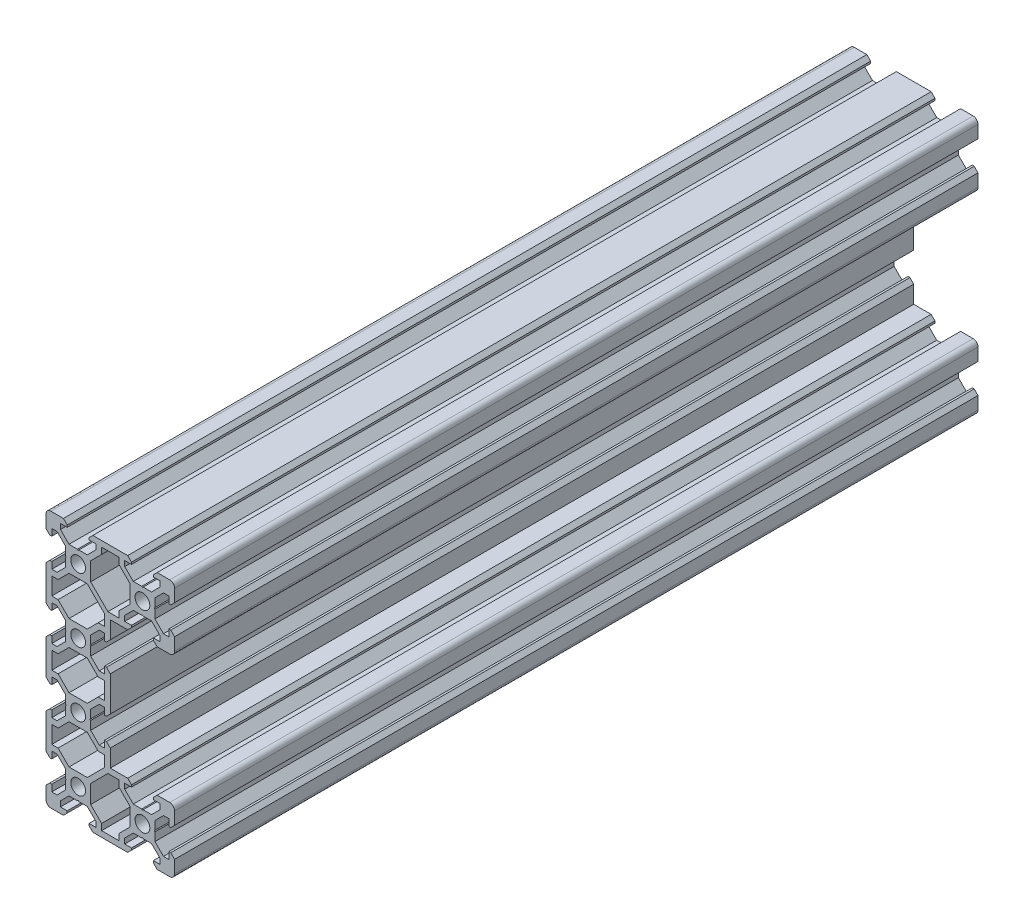
SolidWorks part; units mm, degrees
material "6061-T6 (SS)"
ref_plane "Front Plane" through (0, 0, 0) normal (0, 0, 1) x (1, 0, 0)
ref_plane "Top Plane" through (0, 0, 0) normal (0, 1, 0) x (1, 0, 0)
ref_plane "Right Plane" through (0, 0, 0) normal (1, 0, 0) x (0, 0, -1)
sketch "Sketch1" plane through (0, 0, 0) normal (0, 0, 1) x (1, 0, 0)
  line L0 (-20, -38.5) -> (-20, 38.5)
  line L1 (-18.5, 40) -> (18.5, 40)
  line L2 (20, 38.5) -> (20, 21.5)
  line L3 (18.5, 20) -> (0, 20)
  line L4 (0, 20) -> (0, -20)
  line L5 (0, 0) -> (-20, 0) construction
  line L6 (18.5, -20) -> (0, -20)
  line L7 (20, -38.5) -> (20, -21.5)
  line L8 (-18.5, -40) -> (18.5, -40)
  line L9 (20, 30) -> (10, 30) construction
  line L10 (-10, 0) -> (-10, 10) construction
  arc A0 (-18.5, -40) -> (-20, -38.5) centre (-18.5, -38.5) cw
  arc A1 (20, -38.5) -> (18.5, -40) centre (18.5, -38.5) cw
  arc A2 (18.5, -20) -> (20, -21.5) centre (18.5, -21.5) cw
  arc A3 (20, 21.5) -> (18.5, 20) centre (18.5, 21.5) cw
  arc A4 (18.5, 40) -> (20, 38.5) centre (18.5, 38.5) cw
  arc A5 (-20, 38.5) -> (-18.5, 40) centre (-18.5, 38.5) cw
  circle A6 centre (10, 30) radius 2.3
  circle A7 centre (-10, 30) radius 2.3
  circle A8 centre (-10, 10) radius 2.3
  circle A9 centre (-10, -10) radius 2.3
  circle A10 centre (10, -30) radius 2.3
  circle A11 centre (-10, -30) radius 2.3
  point P13 (-20, -40)
  point P16 (20, -40)
  point P19 (20, -20)
  point P22 (20, 20)
  point P25 (20, 40)
  point P28 (-20, 40)
  line B0 (-10, 30) -> (-10, 40) construction
  line B1 (-10, 33.69) -> (-10.21, 33.9)
  line B2 (-10.21, 33.9) -> (-12.8393, 33.9)
  line B3 (-12.8393, 33.9) -> (-15.5, 36.5607)
  line B4 (-15.5, 36.5607) -> (-15.5, 38.2)
  line B5 (-15.5, 38.2) -> (-13.395, 38.2)
  line B6 (-13.395, 38.2) -> (-13.395, 38.815)
  line B7 (-13.395, 38.815) -> (-14.58, 40)
  line B8 (-14.58, 40) -> (-5.42, 40)
  line B9 (-10, 30) -> (-15.9132, 35.9132) construction
  line B10 (-6.605, 38.815) -> (-5.42, 40)
  line B11 (-6.605, 38.2) -> (-6.605, 38.815)
  line B12 (-4.5, 38.2) -> (-6.605, 38.2)
  line B13 (-4.5, 36.5607) -> (-4.5, 38.2)
  line B14 (-7.1607, 33.9) -> (-4.5, 36.5607)
  line B15 (-9.79, 33.9) -> (-7.1607, 33.9)
  line B16 (-10, 33.69) -> (-9.79, 33.9)
  line B17 (10, 30) -> (10, 40) construction
  line B18 (10, 33.69) -> (9.79, 33.9)
  line B19 (9.79, 33.9) -> (7.1607, 33.9)
  line B20 (7.1607, 33.9) -> (4.5, 36.5607)
  line B21 (4.5, 36.5607) -> (4.5, 38.2)
  line B22 (4.5, 38.2) -> (6.605, 38.2)
  line B23 (6.605, 38.2) -> (6.605, 38.815)
  line B24 (6.605, 38.815) -> (5.42, 40)
  line B25 (5.42, 40) -> (14.58, 40)
  line B26 (10, 30) -> (4.0868, 35.9132) construction
  line B27 (13.395, 38.815) -> (14.58, 40)
  line B28 (13.395, 38.2) -> (13.395, 38.815)
  line B29 (15.5, 38.2) -> (13.395, 38.2)
  line B30 (15.5, 36.5607) -> (15.5, 38.2)
  line B31 (12.8393, 33.9) -> (15.5, 36.5607)
  line B32 (10.21, 33.9) -> (12.8393, 33.9)
  line B33 (10, 33.69) -> (10.21, 33.9)
  line B34 (10, -30) -> (10, -20) construction
  line B35 (10, -26.31) -> (9.79, -26.1)
  line B36 (9.79, -26.1) -> (7.1607, -26.1)
  line B37 (7.1607, -26.1) -> (4.5, -23.4393)
  line B38 (4.5, -23.4393) -> (4.5, -21.8)
  line B39 (4.5, -21.8) -> (6.605, -21.8)
  line B40 (6.605, -21.8) -> (6.605, -21.185)
  line B41 (6.605, -21.185) -> (5.42, -20)
  line B42 (5.42, -20) -> (14.58, -20)
  line B43 (10, -30) -> (4.0868, -24.0868) construction
  line B44 (13.395, -21.185) -> (14.58, -20)
  line B45 (13.395, -21.8) -> (13.395, -21.185)
  line B46 (15.5, -21.8) -> (13.395, -21.8)
  line B47 (15.5, -23.4393) -> (15.5, -21.8)
  line B48 (12.8393, -26.1) -> (15.5, -23.4393)
  line B49 (10.21, -26.1) -> (12.8393, -26.1)
  line B50 (10, -26.31) -> (10.21, -26.1)
  line B51 (-10, 30) -> (-20, 30) construction
  line B52 (-13.69, 30) -> (-13.9, 29.79)
  line B53 (-13.9, 29.79) -> (-13.9, 27.1607)
  line B54 (-13.9, 27.1607) -> (-16.5607, 24.5)
  line B55 (-16.5607, 24.5) -> (-18.2, 24.5)
  line B56 (-18.2, 24.5) -> (-18.2, 26.605)
  line B57 (-18.2, 26.605) -> (-18.815, 26.605)
  line B58 (-18.815, 26.605) -> (-20, 25.42)
  line B59 (-20, 25.42) -> (-20, 34.58)
  line B60 (-10, 30) -> (-15.9132, 24.0868) construction
  line B61 (-18.815, 33.395) -> (-20, 34.58)
  line B62 (-18.2, 33.395) -> (-18.815, 33.395)
  line B63 (-18.2, 35.5) -> (-18.2, 33.395)
  line B64 (-16.5607, 35.5) -> (-18.2, 35.5)
  line B65 (-13.9, 32.8393) -> (-16.5607, 35.5)
  line B66 (-13.9, 30.21) -> (-13.9, 32.8393)
  line B67 (-13.69, 30) -> (-13.9, 30.21)
  line B68 (-10, 10) -> (-20, 10) construction
  line B69 (-13.69, 10) -> (-13.9, 9.79)
  line B70 (-13.9, 9.79) -> (-13.9, 7.1607)
  line B71 (-13.9, 7.1607) -> (-16.5607, 4.5)
  line B72 (-16.5607, 4.5) -> (-18.2, 4.5)
  line B73 (-18.2, 4.5) -> (-18.2, 6.605)
  line B74 (-18.2, 6.605) -> (-18.815, 6.605)
  line B75 (-18.815, 6.605) -> (-20, 5.42)
  line B76 (-20, 5.42) -> (-20, 14.58)
  line B77 (-10, 10) -> (-15.9132, 4.0868) construction
  line B78 (-18.815, 13.395) -> (-20, 14.58)
  line B79 (-18.2, 13.395) -> (-18.815, 13.395)
  line B80 (-18.2, 15.5) -> (-18.2, 13.395)
  line B81 (-16.5607, 15.5) -> (-18.2, 15.5)
  line B82 (-13.9, 12.8393) -> (-16.5607, 15.5)
  line B83 (-13.9, 10.21) -> (-13.9, 12.8393)
  line B84 (-13.69, 10) -> (-13.9, 10.21)
  line B85 (-10, -10) -> (-20, -10) construction
  line B86 (-13.69, -10) -> (-13.9, -10.21)
  line B87 (-13.9, -10.21) -> (-13.9, -12.8393)
  line B88 (-13.9, -12.8393) -> (-16.5607, -15.5)
  line B89 (-16.5607, -15.5) -> (-18.2, -15.5)
  line B90 (-18.2, -15.5) -> (-18.2, -13.395)
  line B91 (-18.2, -13.395) -> (-18.815, -13.395)
  line B92 (-18.815, -13.395) -> (-20, -14.58)
  line B93 (-20, -14.58) -> (-20, -5.42)
  line B94 (-10, -10) -> (-15.9132, -15.9132) construction
  line B95 (-18.815, -6.605) -> (-20, -5.42)
  line B96 (-18.2, -6.605) -> (-18.815, -6.605)
  line B97 (-18.2, -4.5) -> (-18.2, -6.605)
  line B98 (-16.5607, -4.5) -> (-18.2, -4.5)
  line B99 (-13.9, -7.1607) -> (-16.5607, -4.5)
  line B100 (-13.9, -9.79) -> (-13.9, -7.1607)
  line B101 (-13.69, -10) -> (-13.9, -9.79)
  line B102 (-10, -30) -> (-20, -30) construction
  line B103 (-13.69, -30) -> (-13.9, -30.21)
  line B104 (-13.9, -30.21) -> (-13.9, -32.8393)
  line B105 (-13.9, -32.8393) -> (-16.5607, -35.5)
  line B106 (-16.5607, -35.5) -> (-18.2, -35.5)
  line B107 (-18.2, -35.5) -> (-18.2, -33.395)
  line B108 (-18.2, -33.395) -> (-18.815, -33.395)
  line B109 (-18.815, -33.395) -> (-20, -34.58)
  line B110 (-20, -34.58) -> (-20, -25.42)
  line B111 (-10, -30) -> (-15.9132, -35.9132) construction
  line B112 (-18.815, -26.605) -> (-20, -25.42)
  line B113 (-18.2, -26.605) -> (-18.815, -26.605)
  line B114 (-18.2, -24.5) -> (-18.2, -26.605)
  line B115 (-16.5607, -24.5) -> (-18.2, -24.5)
  line B116 (-13.9, -27.1607) -> (-16.5607, -24.5)
  line B117 (-13.9, -29.79) -> (-13.9, -27.1607)
  line B118 (-13.69, -30) -> (-13.9, -29.79)
  line B119 (-10, -30) -> (-10, -40) construction
  line B120 (-10, -33.69) -> (-9.79, -33.9)
  line B121 (-9.79, -33.9) -> (-7.1607, -33.9)
  line B122 (-7.1607, -33.9) -> (-4.5, -36.5607)
  line B123 (-4.5, -36.5607) -> (-4.5, -38.2)
  line B124 (-4.5, -38.2) -> (-6.605, -38.2)
  line B125 (-6.605, -38.2) -> (-6.605, -38.815)
  line B126 (-6.605, -38.815) -> (-5.42, -40)
  line B127 (-5.42, -40) -> (-14.58, -40)
  line B128 (-10, -30) -> (-4.0868, -35.9132) construction
  line B129 (-13.395, -38.815) -> (-14.58, -40)
  line B130 (-13.395, -38.2) -> (-13.395, -38.815)
  line B131 (-15.5, -38.2) -> (-13.395, -38.2)
  line B132 (-15.5, -36.5607) -> (-15.5, -38.2)
  line B133 (-12.8393, -33.9) -> (-15.5, -36.5607)
  line B134 (-10.21, -33.9) -> (-12.8393, -33.9)
  line B135 (-10, -33.69) -> (-10.21, -33.9)
  line B136 (10, -30) -> (10, -40) construction
  line B137 (10, -33.69) -> (10.21, -33.9)
  line B138 (10.21, -33.9) -> (12.8393, -33.9)
  line B139 (12.8393, -33.9) -> (15.5, -36.5607)
  line B140 (15.5, -36.5607) -> (15.5, -38.2)
  line B141 (15.5, -38.2) -> (13.395, -38.2)
  line B142 (13.395, -38.2) -> (13.395, -38.815)
  line B143 (13.395, -38.815) -> (14.58, -40)
  line B144 (14.58, -40) -> (5.42, -40)
  line B145 (10, -30) -> (15.9132, -35.9132) construction
  line B146 (6.605, -38.815) -> (5.42, -40)
  line B147 (6.605, -38.2) -> (6.605, -38.815)
  line B148 (4.5, -38.2) -> (6.605, -38.2)
  line B149 (4.5, -36.5607) -> (4.5, -38.2)
  line B150 (7.1607, -33.9) -> (4.5, -36.5607)
  line B151 (9.79, -33.9) -> (7.1607, -33.9)
  line B152 (10, -33.69) -> (9.79, -33.9)
  line B153 (10, 30) -> (10, 20) construction
  line B154 (10, 26.31) -> (10.21, 26.1)
  line B155 (10.21, 26.1) -> (12.8393, 26.1)
  line B156 (12.8393, 26.1) -> (15.5, 23.4393)
  line B157 (15.5, 23.4393) -> (15.5, 21.8)
  line B158 (15.5, 21.8) -> (13.395, 21.8)
  line B159 (13.395, 21.8) -> (13.395, 21.185)
  line B160 (13.395, 21.185) -> (14.58, 20)
  line B161 (14.58, 20) -> (5.42, 20)
  line B162 (10, 30) -> (15.9132, 24.0868) construction
  line B163 (6.605, 21.185) -> (5.42, 20)
  line B164 (6.605, 21.8) -> (6.605, 21.185)
  line B165 (4.5, 21.8) -> (6.605, 21.8)
  line B166 (4.5, 23.4393) -> (4.5, 21.8)
  line B167 (7.1607, 26.1) -> (4.5, 23.4393)
  line B168 (9.79, 26.1) -> (7.1607, 26.1)
  line B169 (10, 26.31) -> (9.79, 26.1)
  line B170 (-10, 10) -> (0, 10) construction
  line B171 (-6.31, 10) -> (-6.1, 10.21)
  line B172 (-6.1, 10.21) -> (-6.1, 12.8393)
  line B173 (-6.1, 12.8393) -> (-3.4393, 15.5)
  line B174 (-3.4393, 15.5) -> (-1.8, 15.5)
  line B175 (-1.8, 15.5) -> (-1.8, 13.395)
  line B176 (-1.8, 13.395) -> (-1.185, 13.395)
  line B177 (-1.185, 13.395) -> (0, 14.58)
  line B178 (0, 14.58) -> (0, 5.42)
  line B179 (-10, 10) -> (-4.0868, 15.9132) construction
  line B180 (-1.185, 6.605) -> (0, 5.42)
  line B181 (-1.8, 6.605) -> (-1.185, 6.605)
  line B182 (-1.8, 4.5) -> (-1.8, 6.605)
  line B183 (-3.4393, 4.5) -> (-1.8, 4.5)
  line B184 (-6.1, 7.1607) -> (-3.4393, 4.5)
  line B185 (-6.1, 9.79) -> (-6.1, 7.1607)
  line B186 (-6.31, 10) -> (-6.1, 9.79)
  line B187 (-10, -10) -> (0, -10) construction
  line B188 (-6.31, -10) -> (-6.1, -9.79)
  line B189 (-6.1, -9.79) -> (-6.1, -7.1607)
  line B190 (-6.1, -7.1607) -> (-3.4393, -4.5)
  line B191 (-3.4393, -4.5) -> (-1.8, -4.5)
  line B192 (-1.8, -4.5) -> (-1.8, -6.605)
  line B193 (-1.8, -6.605) -> (-1.185, -6.605)
  line B194 (-1.185, -6.605) -> (0, -5.42)
  line B195 (0, -5.42) -> (0, -14.58)
  line B196 (-10, -10) -> (-4.0868, -4.0868) construction
  line B197 (-1.185, -13.395) -> (0, -14.58)
  line B198 (-1.8, -13.395) -> (-1.185, -13.395)
  line B199 (-1.8, -15.5) -> (-1.8, -13.395)
  line B200 (-3.4393, -15.5) -> (-1.8, -15.5)
  line B201 (-6.1, -12.8393) -> (-3.4393, -15.5)
  line B202 (-6.1, -10.21) -> (-6.1, -12.8393)
  line B203 (-6.31, -10) -> (-6.1, -10.21)
  line B204 (10, -30) -> (20, -30) construction
  line B205 (13.69, -30) -> (13.9, -29.79)
  line B206 (13.9, -29.79) -> (13.9, -27.1607)
  line B207 (13.9, -27.1607) -> (16.5607, -24.5)
  line B208 (16.5607, -24.5) -> (18.2, -24.5)
  line B209 (18.2, -24.5) -> (18.2, -26.605)
  line B210 (18.2, -26.605) -> (18.815, -26.605)
  line B211 (18.815, -26.605) -> (20, -25.42)
  line B212 (20, -25.42) -> (20, -34.58)
  line B213 (10, -30) -> (15.9132, -24.0868) construction
  line B214 (18.815, -33.395) -> (20, -34.58)
  line B215 (18.2, -33.395) -> (18.815, -33.395)
  line B216 (18.2, -35.5) -> (18.2, -33.395)
  line B217 (16.5607, -35.5) -> (18.2, -35.5)
  line B218 (13.9, -32.8393) -> (16.5607, -35.5)
  line B219 (13.9, -30.21) -> (13.9, -32.8393)
  line B220 (13.69, -30) -> (13.9, -30.21)
  line B221 (10, 30) -> (20, 30) construction
  line B222 (13.69, 30) -> (13.9, 30.21)
  line B223 (13.9, 30.21) -> (13.9, 32.8393)
  line B224 (13.9, 32.8393) -> (16.5607, 35.5)
  line B225 (16.5607, 35.5) -> (18.2, 35.5)
  line B226 (18.2, 35.5) -> (18.2, 33.395)
  line B227 (18.2, 33.395) -> (18.815, 33.395)
  line B228 (18.815, 33.395) -> (20, 34.58)
  line B229 (20, 34.58) -> (20, 25.42)
  line B230 (10, 30) -> (15.9132, 35.9132) construction
  line B231 (18.815, 26.605) -> (20, 25.42)
  line B232 (18.2, 26.605) -> (18.815, 26.605)
  line B233 (18.2, 24.5) -> (18.2, 26.605)
  line B234 (16.5607, 24.5) -> (18.2, 24.5)
  line B235 (13.9, 27.1607) -> (16.5607, 24.5)
  line B236 (13.9, 29.79) -> (13.9, 27.1607)
  line B237 (13.69, 30) -> (13.9, 29.79)
  line B238 (-18.2, -2.7) -> (-18.2, 2.7)
  line B239 (-18.2, 2.7) -> (-16.2393, 2.7)
  line B240 (-16.2393, 2.7) -> (-12.8393, 6.1)
  line B241 (-12.8393, 6.1) -> (-7.1607, 6.1)
  line B242 (-10, 6.1) -> (-10, 0) construction
  line B243 (-10, 0) -> (-18.2, 0) construction
  line B244 (-3.7607, 2.7) -> (-7.1607, 6.1)
  line B245 (-1.8, 2.7) -> (-3.7607, 2.7)
  line B246 (-1.8, -2.7) -> (-1.8, 2.7)
  line B247 (-1.8, -2.7) -> (-3.7607, -2.7)
  line B248 (-3.7607, -2.7) -> (-7.1607, -6.1)
  line B249 (-12.8393, -6.1) -> (-7.1607, -6.1)
  line B250 (-16.2393, -2.7) -> (-12.8393, -6.1)
  line B251 (-18.2, -2.7) -> (-16.2393, -2.7)
  line B252 (-10, 6.1) -> (-10, 10) construction
  line B253 (-10, 10) -> (-15.0927, 4.9073) construction
  line B254 (-18.2, 17.3) -> (-18.2, 22.7)
  line B255 (-18.2, 22.7) -> (-16.2393, 22.7)
  line B256 (-16.2393, 22.7) -> (-12.8393, 26.1)
  line B257 (-12.8393, 26.1) -> (-7.1607, 26.1)
  line B258 (-10, 26.1) -> (-10, 20) construction
  line B259 (-10, 20) -> (-18.2, 20) construction
  line B260 (-1.8, 17.3) -> (-3.7607, 17.3)
  line B261 (-3.7607, 17.3) -> (-7.1607, 13.9)
  line B262 (-12.8393, 13.9) -> (-7.1607, 13.9)
  line B263 (-16.2393, 17.3) -> (-12.8393, 13.9)
  line B264 (-18.2, 17.3) -> (-16.2393, 17.3)
  line B265 (-10, 26.1) -> (-10, 30) construction
  line B266 (-10, 30) -> (-15.0927, 24.9073) construction
  line B267 (-7.1607, 26.1) -> (-1.8, 20.7393)
  line B268 (-1.8, 17.3) -> (-1.8, 20.7393)
  line B269 (2.7, -38.2) -> (-2.7, -38.2)
  line B270 (-2.7, -38.2) -> (-2.7, -36.2393)
  line B271 (-2.7, -36.2393) -> (-6.1, -32.8393)
  line B272 (-6.1, -32.8393) -> (-6.1, -27.1607)
  line B273 (-6.1, -30) -> (0, -30) construction
  line B274 (0, -30) -> (0, -38.2) construction
  line B275 (2.7, -21.8) -> (2.7, -23.7607)
  line B276 (2.7, -23.7607) -> (6.1, -27.1607)
  line B277 (6.1, -32.8393) -> (6.1, -27.1607)
  line B278 (2.7, -36.2393) -> (6.1, -32.8393)
  line B279 (2.7, -38.2) -> (2.7, -36.2393)
  line B280 (-6.1, -30) -> (-10, -30) construction
  line B281 (-10, -30) -> (-4.9073, -35.0927) construction
  line B282 (-6.1, -27.1607) -> (-0.7393, -21.8)
  line B283 (2.7, -21.8) -> (-0.7393, -21.8)
  line B284 (-18.2, -22.7) -> (-18.2, -17.3)
  line B285 (-18.2, -17.3) -> (-16.2393, -17.3)
  line B286 (-16.2393, -17.3) -> (-12.8393, -13.9)
  line B287 (-12.8393, -13.9) -> (-7.1607, -13.9)
  line B288 (-10, -13.9) -> (-10, -20) construction
  line B289 (-10, -20) -> (-18.2, -20) construction
  line B290 (-12.8393, -26.1) -> (-7.1607, -26.1)
  line B291 (-16.2393, -22.7) -> (-12.8393, -26.1)
  line B292 (-18.2, -22.7) -> (-16.2393, -22.7)
  line B293 (-10, -13.9) -> (-10, -10) construction
  line B294 (-10, -10) -> (-15.0927, -15.0927) construction
  line B295 (-3.7607, -17.3) -> (-7.1607, -13.9)
  line B296 (-1.8, -17.3) -> (-3.7607, -17.3)
  line B297 (-1.8, -17.3) -> (-1.8, -20.7393)
  line B298 (-1.8, -20.7393) -> (-7.1607, -26.1)
  line B299 (-2.7, 38.2) -> (2.7, 38.2)
  line B300 (2.7, 38.2) -> (2.7, 36.2393)
  line B301 (2.7, 36.2393) -> (6.1, 32.8393)
  line B302 (6.1, 32.8393) -> (6.1, 27.1607)
  line B303 (6.1, 30) -> (0, 30) construction
  line B304 (0, 30) -> (0, 38.2) construction
  line B305 (-6.1, 32.8393) -> (-6.1, 27.1607)
  line B306 (-2.7, 36.2393) -> (-6.1, 32.8393)
  line B307 (-2.7, 38.2) -> (-2.7, 36.2393)
  line B308 (6.1, 30) -> (10, 30) construction
  line B309 (10, 30) -> (4.9073, 35.0927) construction
  line B310 (2.7, 23.7607) -> (6.1, 27.1607)
  line B311 (2.7, 21.8) -> (2.7, 23.7607)
  line B312 (2.7, 21.8) -> (-0.7393, 21.8)
  line B313 (-0.7393, 21.8) -> (-6.1, 27.1607)
  dimension "D3" = 1.5
  dimension "D6" = 4.6
  dimension "D7" = 20
  dimension "D8" = 20
  dimension "D1" = 40
  dimension "D2" = 80
  dimension "D4" = 20
  dimension "D5" = 20
sketch_block_instance "V Slot 2-1"
sketch_block "V Slot 2" parameters "D1"=10, "D2"=11, "D3"=4.3, "D4"=1.8, "D5"=0.21, "D6"=45, "D7"=9.16, "D8"=1.5, "D9"=6.79
sketch_block_instance "V Slot 2-2"
sketch_block_instance "V Slot 2-3"
sketch_block_instance "V Slot 2-4"
sketch_block_instance "V Slot 2-5"
sketch_block_instance "V Slot 2-6"
sketch_block_instance "V Slot 2-7"
sketch_block_instance "V Slot 2-8"
sketch_block_instance "V Slot 2-9"
sketch_block_instance "V Slot 2-10"
sketch_block_instance "V Slot 2-11"
sketch_block_instance "V Slot 2-12"
sketch_block_instance "V Slot 2-13"
sketch_block_instance "V Slot 2-14"
sketch_block_instance "Center Cutout 1-1"
sketch_block "Center Cutout 1" parameters "D1"=5.4, "D2"=12.2, "D3"=8.2, "D4"=45, "D5"=10, "D6"=1.5
sketch_block_instance "Corner Cutout 1-1"
sketch_block "Corner Cutout 1" parameters "D1"=5.4, "D2"=12.2, "D3"=8.2, "D4"=45, "D5"=10, "D6"=1.5
sketch_block_instance "Corner Cutout 1-2"
sketch_block_instance "Corner Cutout 2-1"
sketch_block "Corner Cutout 2" parameters "D1"=5.4, "D2"=12.2, "D3"=8.2, "D4"=45, "D5"=10, "D6"=1.5
sketch_block_instance "Corner Cutout 2-2"
extrude "Boss-Extrude1" add sketch "Sketch1" along normal blind 250 contours B237 B222 B223 B224 B225 B226 B227 B228 L2 A4 L1 B27 B28 B29 B30 B31 B32 B33 B18 B19 B20 B21 B22 B23 B24 B10 B11 B12 B13 B14 B15 B16 B1 B2 B3 B4 B5 B6 B7 A5 L0 B61 B62 B63 B64 B65 B66 B67 B52 region at (-19.1056, -36.54, 0)
